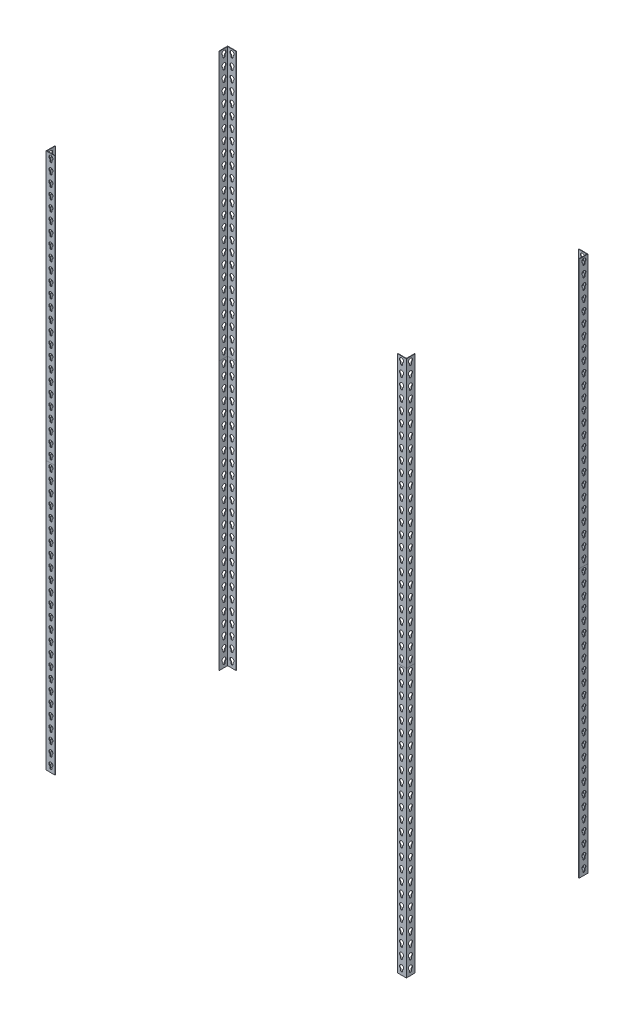
SolidWorks part; units mm, degrees
material "Plain Carbon Steel"
ref_plane "Front Plane" through (0, 0, 0) normal (0, 0, 1) x (1, 0, 0)
ref_plane "Top Plane" through (0, 0, 0) normal (0, 1, 0) x (1, 0, 0)
ref_plane "Right Plane" through (0, 0, 0) normal (1, 0, 0) x (0, 0, -1)
sketch "Sketch1" plane through (0, 0, 0) normal (0, 1, 0) x (1, 0, 0)
  line L1 (-612.775, -307.975) -> (612.775, -307.975)
  line L2 (-612.775, -307.975) -> (-612.775, 307.975)
  line L3 (-612.775, 307.975) -> (612.775, 307.975)
  line L4 (612.775, -307.975) -> (612.775, 307.975)
  line L5 (-612.775, -307.975) -> (612.775, 307.975) construction
  line L6 (-612.775, 307.975) -> (612.775, -307.975) construction
  point P0 (0, 0)
  dimension "D1" = 1225.55
  dimension "D2" = 615.95
sketch "Sketch2" plane through (0, 0, 0) normal (0, 1, 0) x (1, 0, 0)
  line L0 (612.775, -307.975) -> (612.775, 307.975) construction
  line L1 (-612.775, 307.975) -> (-584.2, 307.975)
  line L2 (-612.775, 307.975) -> (-612.775, 279.4)
  line L3 (-612.775, -307.975) -> (-584.2, -307.975)
  line L4 (612.775, 307.975) -> (612.775, 279.4)
  line L5 (-612.775, 307.975) -> (612.775, 307.975) construction
  line L6 (-612.775, -307.975) -> (-612.775, 307.975) construction
  line L7 (-612.775, -307.975) -> (612.775, -307.975) construction
  line L8 (-614.3625, 309.5625) -> (-614.3625, 279.4)
  line L9 (-614.3625, -309.5625) -> (-584.2, -309.5625)
  line L10 (614.3625, 309.5625) -> (614.3625, 279.4)
  line L11 (-614.3625, 309.5625) -> (-584.2, 309.5625)
  line L12 (-614.3625, 279.4) -> (-612.775, 279.4)
  line L13 (-614.3625, -279.4) -> (-612.775, -279.4)
  line L14 (-584.2, 309.5625) -> (-584.2, 307.975)
  line L15 (584.2, 309.5625) -> (584.2, 307.975)
  line L16 (-584.2, -307.975) -> (-584.2, -309.5625)
  line L17 (584.2, -307.975) -> (584.2, -309.5625)
  line L18 (612.775, 279.4) -> (614.3625, 279.4)
  line L19 (612.775, -279.4) -> (614.3625, -279.4)
  line L20 (584.2, 307.975) -> (612.775, 307.975)
  line L21 (584.2, 309.5625) -> (614.3625, 309.5625)
  line L22 (-612.775, 307.975) -> (612.775, 307.975) construction
  line L23 (584.2, -307.975) -> (612.775, -307.975)
  line L24 (-614.3625, 309.5625) -> (614.3625, 309.5625) construction
  line L25 (584.2, -309.5625) -> (614.3625, -309.5625)
  line L26 (-612.775, -307.975) -> (612.775, -307.975) construction
  line L27 (612.775, -279.4) -> (612.775, -307.975)
  line L28 (-614.3625, -309.5625) -> (614.3625, -309.5625) construction
  line L29 (614.3625, -279.4) -> (614.3625, -309.5625)
  line L30 (612.775, 307.975) -> (612.775, -307.975) construction
  line L31 (-612.775, -279.4) -> (-612.775, -307.975)
  line L32 (614.3625, 309.5625) -> (614.3625, -309.5625) construction
  line L33 (-614.3625, -279.4) -> (-614.3625, -309.5625)
  line L34 (-612.775, 307.975) -> (-612.775, -307.975) construction
  line L36 (-614.3625, 309.5625) -> (-614.3625, -309.5625) construction
  dimension "D2" = 30.1625
  dimension "D1" = 1.5875
extrude "Boss-Extrude1" add sketch "Sketch2" along normal blind 914.4
ref_plane "Plane1" through (0, 914.4, 0) normal (0, 1, 0) x (1, 0, 0)
split "Split1" [suppressed] bodies to split 104 101 102 103
sketch "Sketch3" plane through (0, 0, 309.5625) normal (0, 0, 1) x (1, 0, 0)
  line L0 (601.6117, 891.0701) -> (601.6117, 896.2172)
  line L1 (597.9922, 902.1318) -> (597.9922, 891.0701) construction
  line L2 (594.3727, 891.0701) -> (594.3727, 896.2172)
  line L3 (584.2, 914.4) -> (614.3625, 914.4) construction
  line L4 (584.2, 914.4) -> (584.2, 0) construction
  arc A0 (594.3727, 896.2172) -> (601.6117, 896.2172) centre (597.9922, 902.1318) ccw construction
  arc A1 (594.3727, 891.0701) -> (601.6117, 891.0701) centre (597.9922, 891.0701) ccw
  arc A2 (601.6117, 896.2172) -> (594.3727, 896.2172) centre (597.9922, 902.1318) ccw
  dimension "D1" = 13.8684
  dimension "D2" = 5.334
  dimension "D3" = 6.858
  dimension "D4" = 7.239
  dimension "D5" = 21.6154
extrude "Cut-Extrude1" cut sketch "Sketch3" against normal through all
mirror "Mirror1" about plane through (0, 0, 0) normal (1, 0, 0) of "Cut-Extrude1"
sketch "Sketch4" plane through (614.3625, 0, 0) normal (1, 0, 0) x (0, 0, -1)
  line L0 (-292.1508, 891.0701) -> (-292.1508, 896.2172)
  line L1 (-299.3898, 891.0701) -> (-299.3898, 896.2172)
  line L3 (-309.5625, 914.4) -> (-279.4, 914.4) construction
  line L4 (-309.5625, 914.4) -> (-309.5625, 0) construction
  line L5 (-295.7703, 902.1318) -> (-295.7703, 891.0701) construction
  arc A0 (-292.1508, 896.2172) -> (-299.3898, 896.2172) centre (-295.7703, 902.1318) ccw
  arc A1 (-299.3898, 891.0701) -> (-292.1508, 891.0701) centre (-295.7703, 891.0701) ccw
  point P10 (-295.5512, 1816.3127)
  dimension "D1" = 13.8684
  dimension "D2" = 5.334
  dimension "D3" = 6.858
  dimension "D4" = 7.239
  dimension "D5" = 21.6154
extrude "Cut-Extrude2" cut sketch "Sketch4" against normal through all
mirror "Mirror2" about plane through (0, 0, 0) normal (0, 0, 1) of "Cut-Extrude2"
pattern_linear "LPattern4" count 25 spacing 36.576 along (0, -1, 0) of "Cut-Extrude1", "Mirror1", "Cut-Extrude2", "Mirror2"
pattern_linear "LPattern5" count 2 spacing 914.4 along (0, 1, 0) of bodies 124 123 122 121
equation "\"D2@Sketch4\"=\"D2@Sketch3\""
equation "\"D3@Sketch4\"=\"D3@Sketch3\""
equation "\"D4@Sketch4\"=\"D4@Sketch3\""
equation "\"D5@Sketch4\"=\"D5@Sketch3\""
equation "\"D1@Sketch4\"=\"D1@Sketch3\""
